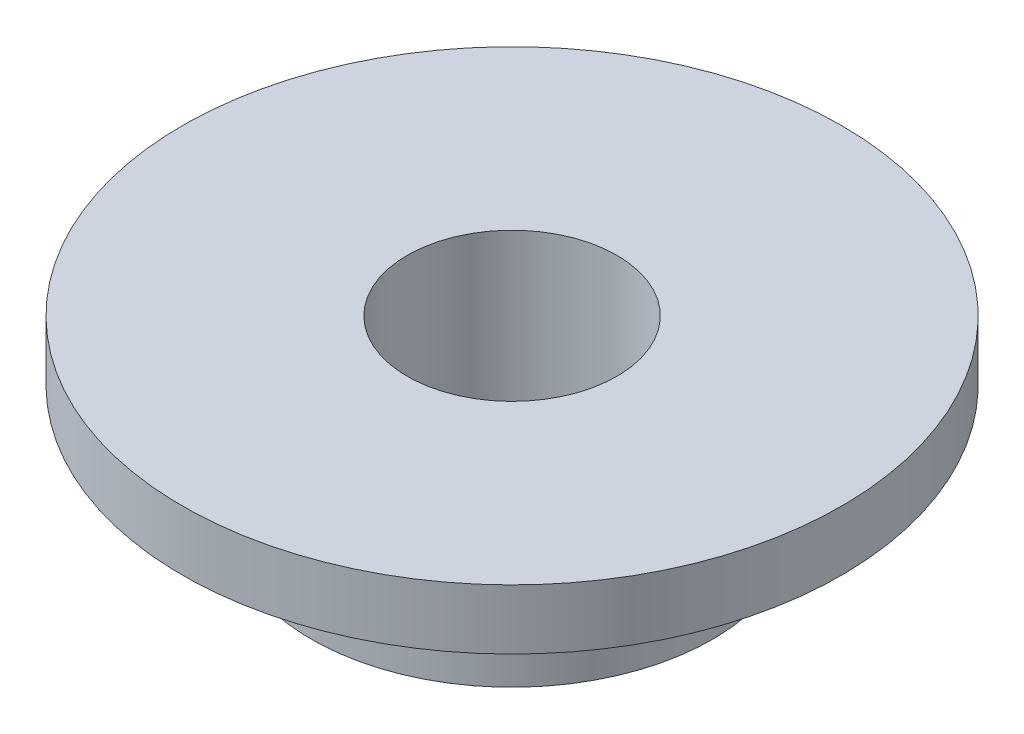
SolidWorks part; units mm, degrees
material "Сталь ШХ15 ГОСТ 801-78"
ref_plane "Plane1" through (0, 0, 0) normal (0, 0, 1) x (1, 0, 0)
ref_plane "Plane2" through (0, 0, 0) normal (0, 1, 0) x (1, 0, 0)
ref_plane "Plane3" through (0, 0, 0) normal (1, 0, 0) x (0, 0, -1)
sketch "Эскиз1" plane through (0, 0, 0) normal (0, 0, 1) x (1, 0, 0)
  line L6 (0, 0) -> (0, 6.4893) construction
  line L7 (3.5, 0) -> (3.5, 6)
  line L8 (3.5, 6) -> (11, 6)
  line L9 (11, 6) -> (11, 4)
  line L10 (11, 4) -> (6.7, 4)
  line L11 (6.7, 4) -> (6.7, 0)
  line L12 (6.7, 0) -> (3.5, 0)
  dimension "D1" = 3.5
  dimension "D2" = 6.7
  dimension "D3" = 11
  dimension "D4" = 2
  dimension "D5" = 6
  dimension "D6" = 0
revolve "Повернуть1" add sketch "Эскиз1" angle 360 about L6
